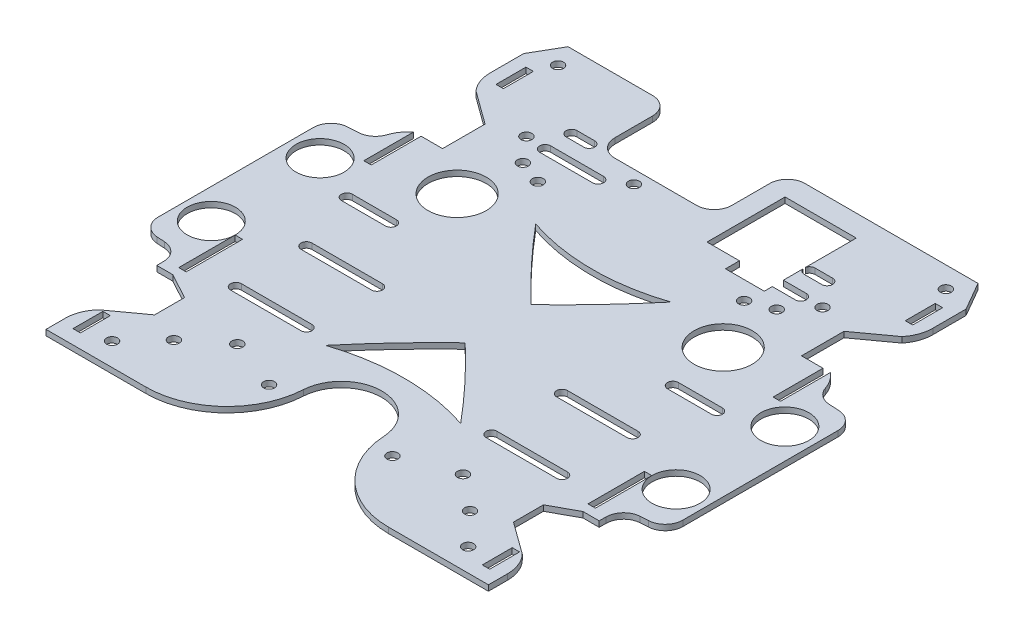
SolidWorks part; units mm, degrees
ref_plane "Front Plane" through (0, 0, 0) normal (0, 0, 1) x (1, 0, 0)
ref_plane "Top Plane" through (0, 0, 0) normal (0, 1, 0) x (1, 0, 0)
ref_plane "Right Plane" through (0, 0, 0) normal (1, 0, 0) x (0, 0, -1)
sketch "Sketch1" plane through (0, 0, 0) normal (0, 1, 0) x (1, 0, 0)
  line L0 (-1000, 0) -> (49000, 0) construction
  line L1 (0, 0) -> (0, 100.3728) construction
  line L5 (-62.75, -55) -> (-34.3696, -55)
  line L6 (62.75, -55) -> (34.3696, -55)
  line L7 (9.55, 82.35) -> (29.75, 82.35)
  line L8 (29.75, 82.35) -> (29.75, 56.25)
  line L10 (9.55, 60.2) -> (9.55, 82.35)
  line L11 (57, 77.5) -> (59.1, 77.5)
  line L12 (59.1, 77.5) -> (59.1, 69)
  line L13 (59.1, 69) -> (57, 69)
  line L14 (57, 69) -> (57, 77.5)
  line L15 (57, 39) -> (57, 47.5)
  line L16 (57, 47.5) -> (59.1, 47.5)
  line L17 (59.1, 47.5) -> (59.1, 39)
  line L18 (59.1, 39) -> (57, 39)
  line L19 (57, 9) -> (57, 17.5) construction
  line L20 (57, 17.5) -> (59.1, 17.5) construction
  line L21 (59.1, 17.5) -> (59.1, 9) construction
  line L22 (59.1, 9) -> (57, 9) construction
  line L35 (57, -51) -> (57, -42.5)
  line L36 (57, -42.5) -> (59.1, -42.5)
  line L37 (59.1, -42.5) -> (59.1, -51)
  line L38 (-62.75, -55) -> (-62.75, 0)
  line L39 (9.55, 60.2) -> (18.75, 60.2)
  line L40 (59.1, -51) -> (57, -51)
  line L42 (18.75, 56.25) -> (18.75, 60.2)
  line L43 (-59.1, -51) -> (-59.1, -42.5)
  line L44 (-59.1, -42.5) -> (-57, -42.5)
  line L45 (-62.75, 0) -> (-62.75, 80.5)
  line L46 (62.75, -55) -> (62.75, 0)
  line L47 (62.75, 0) -> (62.75, 80.5)
  line L48 (-62.75, 80.5) -> (-58.1408, 88.4834)
  line L49 (-58.1408, 88.4834) -> (58.1408, 88.4834)
  line L50 (62.75, 80.5) -> (58.1408, 88.4834)
  line L51 (57, -21) -> (57, -12.5)
  line L52 (57, -12.5) -> (59.1, -12.5)
  line L53 (59.1, -12.5) -> (59.1, -21)
  line L54 (59.1, -21) -> (57, -21)
  line L55 (57, 69) -> (57, 39) construction
  line L56 (-59.1, 69) -> (-59.1, 77.5)
  line L57 (-59.1, 77.5) -> (-57, 77.5)
  line L58 (-57, 77.5) -> (-57, 69)
  line L59 (-57, 69) -> (-59.1, 69)
  line L60 (-59.1, 39) -> (-59.1, 47.5)
  line L61 (-59.1, 47.5) -> (-57, 47.5)
  line L62 (-57, 47.5) -> (-57, 39)
  line L63 (-57, 39) -> (-59.1, 39)
  line L64 (-59.1, 9) -> (-59.1, 17.5) construction
  line L65 (-59.1, 17.5) -> (-57, 17.5) construction
  line L66 (-57, 17.5) -> (-57, 9) construction
  line L67 (-57, 9) -> (-59.1, 9) construction
  line L68 (-59.1, -21) -> (-59.1, -12.5)
  line L69 (-59.1, -12.5) -> (-57, -12.5)
  line L70 (-57, -12.5) -> (-57, -21)
  line L71 (-57, -21) -> (-59.1, -21)
  line L72 (18.75, 56.25) -> (29.75, 56.25)
  line L74 (-57, -42.5) -> (-57, -51)
  line L75 (-57, -51) -> (-59.1, -51)
  circle A2 centre (-15, 64.0223) radius 1.55
  circle A3 centre (-17.5, -36.9777) radius 1.55
  circle A6 centre (17.5, -36.9777) radius 1.55
  arc A7 (-11.4407, -33.3184) -> (-34.3696, -55) centre (-34.3696, -32.0353) cw
  arc A8 (-11.4407, -33.3184) -> (0, -22.5) centre (0, -33.9586) cw
  arc A9 (11.4407, -33.3184) -> (34.3696, -55) centre (34.3696, -32.0353) ccw
  arc A10 (11.4407, -33.3184) -> (0, -22.5) centre (0, -33.9586) ccw
  circle A14 centre (-36, 53.5223) radius 1.55
  circle A17 centre (36, 53.5223) radius 1.55
  circle A23 centre (-32, -31.4777) radius 1.55
  circle A24 centre (-42, -39.4777) radius 1.55
  circle A25 centre (42, -39.4777) radius 1.55
  circle A26 centre (32, -31.4777) radius 1.55
  circle A27 centre (42, 60.5223) radius 1.55
  circle A28 centre (-42, 60.5223) radius 1.55
  circle A31 centre (-29.25, 51.0223) radius 1.55
  circle A32 centre (29.25, 51.0223) radius 1.55
  point P20 (-62.75, 0)
  point P23 (0, 55)
  point P26 (62.75, 0)
  point P63 (24.25, 56.25)
  point P83 (0, 88.4834)
  dimension "D20" = 3.1
  dimension "D21" = 3.1
  dimension "D22" = 42
  dimension "D32" = 36
  dimension "D4" = 101
  dimension "D5" = 17.5
  dimension "D6" = 15
  dimension "D7" = 64.0223
  dimension "D8" = 120
  dimension "D9" = 55
  dimension "D10" = 2
  dimension "D11" = 5
  dimension "D12" = 2.1
  dimension "D13" = 80.5
  dimension "D14" = 125.5
  dimension "D15" = 8.5
  dimension "D16" = 77.5
  dimension "D17" = 30
  dimension "D18" = 114
  dimension "D19" = 22.5
  dimension "D23" = 60.5223
  dimension "D24" = 39.4777
  dimension "D25" = 42
  dimension "D26" = 9.55
  dimension "D27" = 29.75
  dimension "D28" = 82.35
  dimension "D29" = 3.95
  dimension "D30" = 9.2
  dimension "D31" = 26.1
  dimension "D33" = 58.5
  dimension "D34" = 53.5223
  dimension "D35" = 51.0223
  dimension "D36" = 31.4777
  dimension "D37" = 64
extrude "主结构和连接" add sketch "Sketch1" along normal blind 1.6 contours A10 A9 L6 L46 L47 L50 L49 L48 L45 L38 L5 A7 A8 L72 L42 L39 L10 L7 L8 L20 L21 L17 L12 L13 L14 L15 L19 region at (-0.5961, 0, -18.3319)
sketch "外部切除点示意-1" plane through (0, 0, 0) normal (0, 1, 0) x (1, 0, 0)
  line L0 (-58.1408, 88.4834) -> (58.1408, 88.4834) construction
  line L1 (0, 0) -> (-149.6598, 0) construction
  line L2 (0, -1000) -> (0, 49000) construction
  line L3 (-41.25, 28.3195) -> (-41.2859, -7.3505) construction
  line L4 (41.25, 28.3195) -> (41.2859, -7.3505) construction
  line L5 (4.0667, 88.4834) -> (4.0667, 67.7334)
  line L6 (-41.25, 28.3195) -> (-62.75, 28.3195)
  line L7 (4.0667, 67.7334) -> (-29.1468, 67.7334)
  line L8 (-29.1468, 67.7334) -> (-29.1468, 88.4834)
  line L10 (-29.1468, 88.4834) -> (4.0667, 88.4834)
  line L11 (-62.75, 0) -> (-62.75, 80.5) construction
  line L12 (-62.75, 28.3195) -> (-62.75, -7.3505)
  line L13 (-62.75, -55) -> (-62.75, 0) construction
  line L14 (-62.75, -7.3505) -> (-41.2859, -7.3505)
  line L15 (41.25, 28.3195) -> (62.75, 28.3195)
  line L16 (62.75, 28.3195) -> (62.75, -7.3505)
  line L17 (62.75, -7.3505) -> (41.2859, -7.3505)
  line L18 (-62.0244, -25.5795) -> (-62.75, -26.1067) construction
  line L19 (60.406, 64.6074) -> (50.9062, 57.7054)
  line L20 (-62.75, -26.1067) -> (-62.75, -41.5627) construction
  line L21 (-60.4273, -42.3422) -> (-53.5015, -37.3103) construction
  line L22 (-53.3356, -36.2627) -> (-53.6571, -35.8201) construction
  line L23 (-61.7688, -41.7717) -> (-61.4749, -42.1762) construction
  line L24 (-60.6553, -26.188) -> (-60.9768, -25.7455) construction
  line L25 (-62.75, 62.6074) -> (-62.75, 47.1514) construction
  line L26 (62.75, 64.6074) -> (60.406, 64.6074)
  line L27 (-62.75, 47.1514) -> (-62.0244, 46.6242) construction
  line L28 (-60.6553, 47.2327) -> (-60.9768, 46.7901) construction
  line L29 (-53.3356, 57.3074) -> (-53.6571, 56.8648) construction
  line L30 (-53.5015, 58.355) -> (-60.4273, 63.3868) construction
  line L31 (-61.4749, 63.2209) -> (-61.7688, 62.8164) construction
  line L32 (-62.75, 64.6074) -> (-60.406, 64.6074)
  line L33 (-60.406, 64.6074) -> (-50.9062, 57.7054)
  line L34 (-50.9062, 57.7054) -> (-50.9062, 45.6514)
  line L35 (-50.9062, 45.6514) -> (-62.75, 45.6514)
  line L36 (-62.75, 45.6514) -> (-62.75, 64.6074)
  line L37 (-62.75, -23.5795) -> (-58.187, -23.5795)
  line L38 (-58.187, -23.5795) -> (-50.9062, -27.5482)
  line L39 (-50.9062, -27.5482) -> (-50.9062, -36.0427)
  line L41 (-62.75, -42.6524) -> (-62.75, -23.5795)
  line L42 (-50.9062, -36.0427) -> (-60.0037, -42.6524)
  line L43 (-60.0037, -42.6524) -> (-62.75, -42.6524)
  line L44 (62.75, 45.6514) -> (62.75, 64.6074)
  line L45 (50.9062, 45.6514) -> (62.75, 45.6514)
  line L46 (50.9062, 57.7054) -> (50.9062, 45.6514)
  line L47 (62.75, -23.5795) -> (58.187, -23.5795)
  line L48 (62.75, -42.6524) -> (62.75, -23.5795)
  line L49 (60.0037, -42.6524) -> (62.75, -42.6524)
  line L50 (50.9062, -36.0427) -> (60.0037, -42.6524)
  line L51 (50.9062, -27.5482) -> (50.9062, -36.0427)
  line L52 (58.187, -23.5795) -> (50.9062, -27.5482)
  arc A0 (-41.25, 28.3195) -> (-41.2859, -7.3505) centre (-78.8424, 10.5223) cw
  arc A1 (-61.7688, 62.8164) -> (-62.75, 62.6074) centre (-62.3756, 63.2573) cw construction
  arc A2 (-62.75, 28.3195) -> (-62.75, -7.3505) centre (-100.3245, 10.4845) cw
  arc A3 (41.25, 28.3195) -> (41.2859, -7.3505) centre (78.8424, 10.5223) ccw
  arc A4 (-61.4749, 63.2209) -> (-60.4273, 63.3868) centre (-60.8681, 62.7801) cw construction
  arc A5 (-53.5015, 58.355) -> (-53.3356, 57.3074) centre (-53.9424, 57.7482) cw construction
  arc A6 (-53.5636, 55.877) -> (-53.6571, 56.8648) centre (-53.0504, 56.4239) cw construction
  arc A7 (-53.5636, 55.877) -> (-59.687, 47.449) centre (-57.1562, 52.0488) cw construction
  arc A8 (-60.6553, 47.2327) -> (-59.687, 47.449) centre (-60.0485, 46.7919) cw construction
  arc A9 (-62.0244, 46.6242) -> (-60.9768, 46.7901) centre (-61.5836, 47.231) ccw construction
  arc A10 (-62.0244, -25.5795) -> (-60.9768, -25.7455) centre (-61.5836, -26.1863) cw construction
  arc A11 (-60.6553, -26.188) -> (-59.687, -26.4043) centre (-60.0485, -25.7472) ccw construction
  arc A12 (-59.687, -26.4043) -> (-53.5636, -34.8324) centre (-57.1562, -31.0041) cw construction
  arc A13 (-53.5636, -34.8324) -> (-53.6571, -35.8201) centre (-53.0504, -35.3793) ccw construction
  arc A14 (-53.3356, -36.2627) -> (-53.5015, -37.3103) centre (-53.9424, -36.7035) cw construction
  arc A15 (-61.7688, -41.7717) -> (-62.75, -41.5627) centre (-62.3756, -42.2126) ccw construction
  arc A16 (62.75, 28.3195) -> (62.75, -7.3505) centre (100.3245, 10.4845) ccw
  arc A17 (-61.4749, -42.1762) -> (-60.4273, -42.3422) centre (-60.8681, -41.7354) ccw construction
  dimension "D3" = 6.25
  dimension "D7" = 6.25
  dimension "D1" = 20.75
  dimension "D2" = 1
  dimension "D4" = 1.5
  dimension "D5" = 2
  dimension "D6" = 0.5
  dimension "D9" = 2
  dimension "D10" = 1.5
sketch "路由器孔位-草图" plane through (0, 0, 0) normal (0, 1, 0) x (1, 0, 0)
  line L0 (-52.5, 69.8447) -> (0, 69.8447) construction
  line L1 (0, 0) -> (0, 100.3728) construction
  line L2 (0, 0) -> (0, 234.4468) construction
  line L3 (0, -201000) -> (0, 249000) construction
  line L4 (0, 0) -> (127.6117, 0) construction
  line L5 (-201000, 0) -> (249000, 0) construction
  line L6 (-52.5, 69.8447) -> (-52.5, -29.6553) construction
  line L7 (-52.5, -29.6553) -> (52.5, -29.6553) construction
  line L8 (52.5, -29.6553) -> (52.5, 69.8447) construction
  line L9 (52.5, 69.8447) -> (0, 69.8447) construction
  line L10 (-52.5, 20.0947) -> (0, 20.0947) construction
  line L11 (-36.25, 67.5947) -> (-31.25, 67.5947) construction
  line L12 (-36.25, 69.1447) -> (-31.25, 69.1447)
  line L13 (-36.25, 66.0447) -> (-31.25, 66.0447)
  line L14 (36.25, 67.5947) -> (31.25, 67.5947) construction
  line L15 (36.25, 69.1447) -> (31.25, 69.1447)
  line L16 (36.25, 66.0447) -> (31.25, 66.0447)
  line L17 (-36.25, 60.0947) -> (-21.25, 60.0947) construction
  line L18 (-36.25, 61.6648) -> (-21.25, 61.6648)
  line L19 (-36.25, 58.5246) -> (-21.25, 58.5246)
  line L20 (36.25, 60.0947) -> (21.25, 60.0947) construction
  line L21 (36.25, 61.6648) -> (21.25, 61.6648)
  line L22 (36.25, 58.5246) -> (21.25, 58.5246)
  line L23 (-52.5, 20.0947) -> (-40, 20.0947) construction
  line L24 (-52.5, 21.6447) -> (-40, 21.6447)
  line L25 (-52.5, 18.5447) -> (-40, 18.5447)
  line L26 (-46.25, -17.6163) -> (-26.25, -17.6163) construction
  line L27 (-46.25, -16.0663) -> (-26.25, -16.0663)
  line L28 (-46.25, -19.1663) -> (-26.25, -19.1663)
  line L29 (46.25, -17.6163) -> (26.25, -17.6163) construction
  line L30 (46.25, -16.0663) -> (26.25, -16.0663)
  line L31 (46.25, -19.1663) -> (26.25, -19.1663)
  line L32 (52.5, 20.0947) -> (40, 20.0947) construction
  line L33 (52.5, 21.6447) -> (40, 21.6447)
  line L34 (52.5, 18.5447) -> (40, 18.5447)
  line L35 (-46.25, 2.3837) -> (-26.25, 2.3837) construction
  line L36 (-46.25, 3.9337) -> (-26.25, 3.9337)
  line L37 (-46.25, 0.8337) -> (-26.25, 0.8337)
  line L38 (46.25, 2.3837) -> (26.25, 2.3837) construction
  line L39 (46.25, 3.9337) -> (26.25, 3.9337)
  line L40 (46.25, 0.8337) -> (26.25, 0.8337)
  circle A0 centre (-52.5, 20.0947) radius 1.55 construction
  circle A1 centre (-33.75, 67.5947) radius 1.55 construction
  circle A2 centre (33.75, 67.5947) radius 1.55 construction
  arc A3 (-36.25, 69.1447) -> (-36.25, 66.0447) centre (-36.25, 67.5947) ccw
  arc A4 (-31.25, 66.0447) -> (-31.25, 69.1447) centre (-31.25, 67.5947) ccw
  arc A5 (36.25, 69.1447) -> (36.25, 66.0447) centre (36.25, 67.5947) cw
  arc A6 (31.25, 66.0447) -> (31.25, 69.1447) centre (31.25, 67.5947) cw
  arc A7 (-36.25, 61.6648) -> (-36.25, 58.5246) centre (-36.25, 60.0947) ccw
  arc A8 (-21.25, 58.5246) -> (-21.25, 61.6648) centre (-21.25, 60.0947) ccw
  arc A9 (36.25, 61.6648) -> (36.25, 58.5246) centre (36.25, 60.0947) cw
  arc A10 (21.25, 58.5246) -> (21.25, 61.6648) centre (21.25, 60.0947) cw
  arc A11 (-52.5, 21.6447) -> (-52.5, 18.5447) centre (-52.5, 20.0947) ccw
  arc A12 (-40, 18.5447) -> (-40, 21.6447) centre (-40, 20.0947) ccw
  arc A13 (-46.25, -16.0663) -> (-46.25, -19.1663) centre (-46.25, -17.6163) ccw
  arc A14 (-26.25, -19.1663) -> (-26.25, -16.0663) centre (-26.25, -17.6163) ccw
  arc A15 (46.25, -16.0663) -> (46.25, -19.1663) centre (46.25, -17.6163) cw
  arc A16 (26.25, -19.1663) -> (26.25, -16.0663) centre (26.25, -17.6163) cw
  arc A17 (52.5, 21.6447) -> (52.5, 18.5447) centre (52.5, 20.0947) cw
  arc A18 (40, 18.5447) -> (40, 21.6447) centre (40, 20.0947) cw
  arc A19 (-46.25, 3.9337) -> (-46.25, 0.8337) centre (-46.25, 2.3837) ccw
  arc A20 (-26.25, 0.8337) -> (-26.25, 3.9337) centre (-26.25, 2.3837) ccw
  arc A21 (46.25, 3.9337) -> (46.25, 0.8337) centre (46.25, 2.3837) cw
  arc A22 (26.25, 0.8337) -> (26.25, 3.9337) centre (26.25, 2.3837) cw
  circle A23 centre (55, 82.5) radius 1.55
  circle A24 centre (55, 82.5) radius 3 construction
  circle A25 centre (-55, 82.5) radius 1.55
  circle A26 centre (-55, 82.5) radius 3 construction
  circle A28 centre (-50.5, -48.5) radius 3 construction
  circle A29 centre (50.5, -48.5) radius 1.55
  circle A30 centre (50.5, -48.5) radius 3 construction
  circle A31 centre (-50.5, -48.5) radius 1.55
  point P24 (-33.75, 67.5947)
  point P29 (-28.75, 60.0947)
  point P32 (33.75, 67.5947)
  point P45 (28.75, 60.0947)
  point P51 (-46.25, 20.0947)
  point P56 (-36.25, -17.6163)
  point P65 (36.25, -17.6163)
  point P72 (46.25, 20.0947)
  point P77 (-36.25, 2.3837)
  point P87 (36.25, 2.3837)
  dimension "D4" = 3.1
  dimension "D11" = 2
  dimension "D12" = 3.1
  dimension "D13" = 6
  dimension "D1" = 105
  dimension "D2" = 99.5
  dimension "D3" = 67.5
  dimension "D5" = 2.25
  dimension "D6" = 5
  dimension "D7" = 12.5
  dimension "D8" = 7.5
  dimension "D9" = 15
  dimension "D10" = 20
  dimension "D14" = 50.5
  dimension "D15" = 55
  dimension "D16" = 82.5
  dimension "D17" = 48.5
extrude "外部干涉切除" cut sketch "外部切除点示意-1" along normal through all contours L10 L8 L7 L5 | L36 L35 L34 L33 L32 | L19 L46 L45 L44 L26 | L43 L42 L39 L38 L37 L41 | L47 L52 L51 L50 L49 L48 | A2 L12 | L16 A16 region at (-12.5401, 0, -78.1084) region at (-61.136, 0, -10.4845) region at (61.136, 0, -10.4845) region at (57.2992, 0, -53.9021) region at (-57.2992, 0, -53.9021) region at (-57.5854, 0, 32.5546) region at (57.5854, 0, 32.5546)
fillet "Fillet1" radius 10 10 edges at (62.75, 0.8, 42.6524) (-62.75, 0.8, 42.6524) (62.75, 0.8, -64.6074) (62.75, 0.8, -45.6514) (62.75, 0.8, -28.3195) (62.75, 0.8, 7.3505) (-62.75, 0.8, -64.6074) (-62.75, 0.8, -45.6514) (-62.75, 0.8, 7.3505) (-62.75, 0.8, -28.3195)
extrude "路由器安装" cut sketch "路由器孔位-草图" along normal through all
sketch "飞控过线-草图" plane through (0, 1.6, 0) normal (0, 1, 0) x (1, 0, 0)
  line L0 (0, 0) -> (0, 53.6886) construction
  line L1 (0, 0) -> (0, 100.3728) construction
  line L2 (0, 0) -> (139.6377, 0) construction
  line L3 (-201000, 0) -> (249000, 0) construction
  line L4 (0, 19.8942) -> (0, 10.5223) construction
  line L5 (0, 10.5223) -> (9.3719, 10.5223) construction
  arc A3 (9.3719, 10.5223) -> (29.8202, 29.7013) centre (187.9553, -159.3904) cw construction
  arc A4 (29.8202, 29.7013) -> (29.8202, -8.6566) centre (87.1283, 10.5223) ccw construction
  arc A5 (29.8202, -8.6566) -> (9.3719, 10.5223) centre (187.9553, 180.4351) cw construction
  circle A6 centre (0, 10.5223) radius 9.3719 construction
  arc A7 (0, 1.1505) -> (19.1789, -19.2978) centre (-169.9128, -177.433) cw
  arc A8 (19.1789, -19.2978) -> (-19.1789, -19.2978) centre (0, -76.6059) ccw
  arc A9 (-19.1789, -19.2978) -> (0, 1.1505) centre (169.9128, -177.433) cw
  arc A10 (-9.3719, 10.5223) -> (-29.8202, -8.6566) centre (-187.9553, 180.4351) cw construction
  arc A11 (-29.8202, -8.6566) -> (-29.8202, 29.7013) centre (-87.1283, 10.5223) ccw construction
  arc A12 (-29.8202, 29.7013) -> (-9.3719, 10.5223) centre (-187.9553, -159.3904) cw construction
  arc A13 (0, 19.8942) -> (-19.1789, 40.3425) centre (169.9128, 198.4777) cw
  arc A14 (-19.1789, 40.3425) -> (19.1789, 40.3425) centre (0, 97.6506) ccw
  arc A15 (19.1789, 40.3425) -> (0, 19.8942) centre (-169.9128, 198.4777) cw
  point P38 (0, 10.5223)
  dimension "D1" = 10.5223
  dimension "D2" = 4
extrude "飞控过线孔" cut sketch "飞控过线-草图" against normal through all
sketch "天线座-底部-草图" plane through (0, 0, 0) normal (0, 1, 0) x (1, 0, 0)
  line L1 (-58.7321, 10.4845) -> (-106.3161, 10.4845) construction
  line L7 (-59.1, 39) -> (-100.6746, 39) construction
  line L8 (-62.75, 37.9263) -> (-74.425, 37.1996)
  line L9 (-74.425, 37.1996) -> (-74.425, -16.2306)
  line L10 (-62.75, -16.9573) -> (-74.425, -16.2306)
  line L11 (-62.75, 37.9263) -> (-56.4592, 37.9263)
  line L12 (-56.4592, 37.9263) -> (-56.4592, -7.7803)
  line L13 (-56.4592, -7.7803) -> (-62.75, -12.4522)
  line L14 (-62.75, -55) -> (-62.75, 0) construction
  line L15 (-62.75, -12.4522) -> (-62.75, -16.9573)
  line L16 (0, 0) -> (0, 126.5696) construction
  line L17 (56.4592, -7.7803) -> (62.75, -12.4522)
  line L18 (56.4592, 37.9263) -> (56.4592, -7.7803)
  line L19 (62.75, 37.9263) -> (56.4592, 37.9263)
  line L20 (62.75, 37.9263) -> (74.425, 37.1996)
  line L21 (74.425, 37.1996) -> (74.425, -16.2306)
  line L22 (62.75, -16.9573) -> (74.425, -16.2306)
  line L23 (62.75, -12.4522) -> (62.75, -16.9573)
  line L24 (77.5, -949.7862) -> (77.5, 49050.2138) construction
  line L25 (-59.1, 39) -> (-59.1, 47.5) construction
  arc A0 (-61.9712, -5.6077) -> (-61.9712, 26.5766) centre (-100.3245, 10.4845) ccw construction
  circle A1 centre (-65.925, 25.9126) radius 6.825
  circle A2 centre (-65.925, -4.9437) radius 6.825
  circle A5 centre (65.925, -4.9437) radius 6.825
  circle A6 centre (65.925, 25.9126) radius 6.825
  circle A8 centre (-37.7389, 36.6044) radius 8.25
  circle A9 centre (37.7389, 36.6044) radius 8.25
  point P20 (-74.425, 10.4845)
  point P22 (-87.75, -7.7803)
  dimension "D2" = 13.65
  dimension "D3" = 77.5
  dimension "D4" = 16.5
  dimension "D1" = 8.5
extrude "天线-底" add sketch "天线座-底部-草图" along normal up to surface (1.6 mm away) from surface up to face at (0, 1.6, -32.3031) starting at face at (46.25, 0, -20.0947)
extrude "天线孔位和安装穿孔" cut sketch "天线座-底部-草图<2>" along normal through all contours A1 | A2 | A6 | A5 | A8 | A9 region at (-65.925, 0, -25.9126) region at (-65.925, 0, 4.9437) region at (65.925, 0, 4.9437) region at (65.925, 0, -25.9126) region at (-37.7389, 0, -36.6044) region at (37.7389, 0, -36.6044)
sketch "天线座-底部-草图<2>" plane through (0, 0, 0) normal (0, 1, 0) x (1, 0, 0) same geometry as "天线座-底部-草图"
sketch "天线座-顶-草图" plane through (0, 0, 0) normal (0, 1, 0) x (1, 0, 0)
  line L1 (-45.5515, 9.3811) -> (-93.1356, 9.3811) construction
  line L7 (-59.1, 39) -> (-100.6746, 39) construction
  line L8 (-62.75, 37.9263) -> (-87.925, 36.1941)
  line L9 (-87.925, 36.1941) -> (-87.925, -17.432)
  line L10 (-62.75, -19.1642) -> (-87.925, -17.432)
  line L11 (-62.75, 37.9263) -> (-56.4592, 37.9263)
  line L12 (-56.4592, 37.9263) -> (-56.4592, -7.7803)
  line L13 (-56.4592, -7.7803) -> (-62.75, -12.4522)
  line L15 (-62.75, -12.4522) -> (-62.75, -19.1642)
  line L16 (0, 0) -> (0, 150.5398) construction
  line L24 (-62.75, -55) -> (-62.75, 0) construction
  line L25 (59.1, 39) -> (100.6746, 39) construction
  line L26 (45.5515, 9.3811) -> (93.1356, 9.3811) construction
  line L27 (62.75, -12.4522) -> (62.75, -19.1642)
  line L28 (56.4592, -7.7803) -> (62.75, -12.4522)
  line L29 (56.4592, 37.9263) -> (56.4592, -7.7803)
  line L30 (62.75, 37.9263) -> (56.4592, 37.9263)
  line L31 (62.75, -19.1642) -> (87.925, -17.432)
  line L32 (87.925, 36.1941) -> (87.925, -17.432)
  line L33 (62.75, 37.9263) -> (87.925, 36.1941)
  ellipse E0 centre (-75.425, 27.4126) end of major axis (-75.425, 34.1876) minor radius 6.25
  ellipse E1 centre (-78.425, -5.9853) end of major axis (-78.425, 0.7897) minor radius 6.25
  ellipse E2 centre (78.425, -5.9853) end of major axis (78.425, 0.7897) minor radius 6.25
  ellipse E3 centre (75.425, 27.4126) end of major axis (75.425, 34.1876) minor radius 6.25
  point P20 (-87.925, 9.3811)
  point P22 (0, 0)
  point P26 (0, 0)
  point P28 (0, 0)
  point P34 (0, 0)
  point P59 (87.925, 9.3811)
  dimension "D2" = 12.5
  dimension "D3" = 9.5
  dimension "D1" = 13.55
  dimension "D4" = 1.5
  dimension "D5" = 12.5
  dimension "D6" = 12.5
  dimension "D7" = 13.55
  dimension "D8" = 3.25
fillet "Fillet2" radius 5 8 edges at (74.425, 0.8, -37.1996) (62.75, 0.8, -37.9263) (62.75, 0.8, 16.9573) (74.425, 0.8, 16.2306) (-62.75, 0.8, 16.9573) (-74.425, 0.8, 16.2306) (-62.75, 0.8, -37.9263) (-74.425, 0.8, -37.1996)
sketch "Sketch4" plane through (0, 1.6, 0) normal (0, 1, 0) x (1, 0, 0)
  line L0 (-59.1, 39) -> (-59.1, 31.5)
  line L1 (-59.1, 31.5) -> (-57, 31.5)
  line L2 (-57, 31.5) -> (-57, 39)
  line L3 (-57, 39) -> (-59.1, 39)
  line L4 (-57, 47.5) -> (-57, 39) construction
  line L5 (-59.1, -5) -> (-59.1, -12.5)
  line L6 (-59.1, -12.5) -> (-57, -12.5)
  line L7 (-57, -12.5) -> (-57, -5)
  line L8 (-57, -5) -> (-59.1, -5)
  line L9 (57, -5) -> (57, -12.5)
  line L10 (57, -12.5) -> (59.1, -12.5)
  line L11 (59.1, -12.5) -> (59.1, -5)
  line L12 (59.1, -5) -> (57, -5)
  line L13 (57, 39) -> (57, 31.5)
  line L14 (57, 31.5) -> (59.1, 31.5)
  line L15 (59.1, 31.5) -> (59.1, 39)
  line L16 (59.1, 39) -> (57, 39)
  line L17 (-57, -12.5) -> (-57, -21) construction
  line L18 (59.1, -12.5) -> (59.1, -21) construction
  line L19 (59.1, 47.5) -> (59.1, 39) construction
  dimension "D1" = 7.5
extrude "额外榫卯-7.5mm" cut sketch "Sketch4" against normal through all
fillet "Fillet3" radius 5 4 edges at (4.0667, 0.8, -88.4834) (4.0667, 0.8, -67.7334) (-29.1468, 0.8, -67.7334) (-29.1468, 0.8, -88.4834)
sketch "Sketch5" plane through (0, 1.6, 0) normal (0, 1, 0) x (1, 0, 0)
  line L0 (57, 69) -> (57, 62.1328)
  line L1 (57, 69) -> (57, 39) construction
  line L2 (60.406, 64.6074) -> (50.9062, 57.7054) construction
  line L3 (57, 62.1328) -> (57, 45.6514)
  line L4 (57, 45.6514) -> (57, -24.2265)
  line L5 (58.187, -23.5795) -> (50.9062, -27.5482) construction
  line L6 (57, -24.2265) -> (57, -42.5)
  line L7 (57, -42.5) -> (57, -42.75)
  line L8 (57, -51) -> (57, -42.5) construction
  line L9 (57, 69) -> (57, 69.25)
  line L10 (57, 69) -> (57, 77.5) construction
  line L11 (57, -42.5) -> (57, -40.4701)
  line L12 (50.9062, -36.0427) -> (60.0037, -42.6524) construction
  dimension "D1" = 0.25
  dimension "D2" = 0.25
